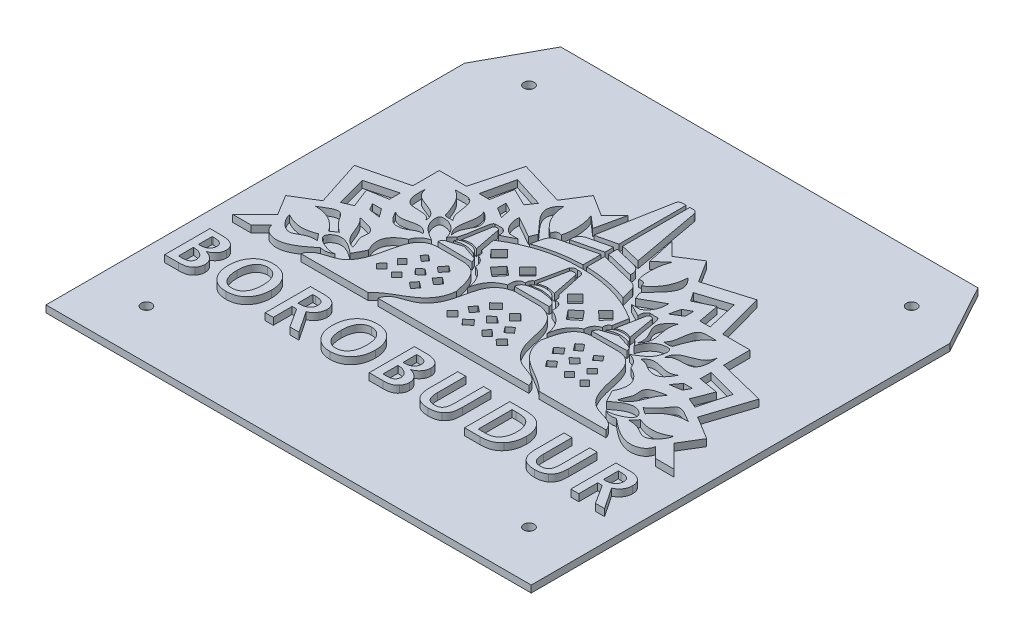
SolidWorks part; units mm, degrees
ref_plane "Front Plane" through (0, 0, 0) normal (0, 0, 1) x (1, 0, 0)
ref_plane "Top Plane" through (0, 0, 0) normal (0, 1, 0) x (1, 0, 0)
ref_plane "Right Plane" through (0, 0, 0) normal (1, 0, 0) x (0, 0, -1)
sketch "Sketch2" plane through (0, 0, 0) normal (0, 1, 0) x (1, 0, 0)
  line L0 (-69.75, 120.33) -> (-69.75, 0)
  line L1 (-69.75, 0) -> (69.75, 0)
  line L2 (69.75, 0) -> (69.75, 120.33)
  line L3 (69.75, 120.33) -> (59.98, 138.2123)
  line L4 (59.98, 138.2123) -> (-59.98, 138.2123)
  line L5 (-59.98, 138.2123) -> (-69.75, 120.33)
  line L6 (-55, 124.11) -> (-55, 14.11) construction
  line L7 (-55, 14.11) -> (55, 14.11) construction
  line L8 (55, 14.11) -> (55, 124.11) construction
  line L9 (55, 124.11) -> (-55, 124.11) construction
  line L10 (0, 14.11) -> (0, 0) construction
  circle A0 centre (-55, 124.11) radius 1.5
  circle A1 centre (55, 124.11) radius 1.5
  circle A2 centre (55, 14.11) radius 1.5
  circle A3 centre (-55, 14.11) radius 1.5
  point P6 (0, 0)
  dimension "D6" = 3
  dimension "D1" = 139.5
  dimension "D2" = 120.33
  dimension "D3" = 118.65
  dimension "D4" = 118.65
  dimension "D5" = 119.96
  dimension "D7" = 110
  dimension "D8" = 110
  dimension "D9" = 14.11
extrude "Boss-Extrude1" add sketch "Sketch2" along normal blind 2
sketch "Sketch5" plane through (0, 2, 0) normal (0, 1, 0) x (1, 0, 0)
  line L0 (-492.273, -111.0065) -> (-56.9397, -111.0065) construction
  line L3 (0, 0) -> (0, 138.2123) construction
  line L4 (59.98, 138.2123) -> (-59.98, 138.2123) construction
  line L5 (-499.4365, -25.4656) -> (-64.1032, -25.4656) construction
  line L6 (0, 47.3754) -> (-21.6859, 47.3754)
  line L7 (-24.6018, 47.3754) -> (-43.8626, 47.3754)
  line L8 (-25.7541, 68.7243) -> (-18.7302, 68.7243)
  line L9 (-22.2422, 68.7243) -> (-22.2422, 47.3754) construction
  line L10 (-3.7057, 68.7243) -> (0, 68.7243)
  line L11 (-19.5144, 78.4449) -> (-18.7302, 74.224)
  line L12 (-1.7255, 82.4366) -> (-3.4837, 74.224)
  line L13 (-1.013, 81.2435) -> (-2.4679, 73.9099)
  line L14 (0, 91.6011) -> (-8.7196, 89.5051)
  line L15 (0, 95.6184) -> (-6.3568, 94.0901)
  line L16 (-6.3568, 94.0901) -> (-2.7736, 113.7579)
  line L17 (-1.4606, 114.8023) -> (0, 114.8023)
  line L18 (0, 90.4895) -> (-10.1933, 87.9731)
  line L19 (-12.4793, 86.3667) -> (-13.4352, 82.7244)
  line L20 (-6.3568, 103.9184) -> (-10.1933, 100.082)
  line L21 (-10.1933, 100.082) -> (-16.2824, 103.9184)
  line L22 (-16.2824, 103.9184) -> (-20.2698, 97.5897)
  line L23 (-20.2698, 97.5897) -> (-33.217, 101.4709)
  line L24 (-33.217, 101.4709) -> (-36.8387, 87.9731)
  line L25 (-36.8387, 87.9731) -> (-44.6751, 87.9731)
  line L26 (-44.6751, 87.9731) -> (-44.6751, 80.3944)
  line L27 (-44.6751, 80.3944) -> (-58.1708, 77.0507)
  line L28 (-58.1708, 77.0507) -> (-53.8631, 63.7358)
  line L29 (-53.8631, 63.7358) -> (-60.5227, 59.6742)
  line L30 (-60.5227, 59.6742) -> (-56.9815, 53.8678)
  line L31 (-56.9815, 53.8678) -> (-63.4739, 47.3754)
  line L32 (-63.4739, 47.3754) -> (-58.1708, 47.3754)
  line L33 (-58.1708, 47.3754) -> (-55.1522, 50.3941)
  line L34 (-46.3062, 54.8983) -> (-44.6751, 52.9547)
  line L35 (-6.3568, 103.9184) -> (-8.1937, 95.6184)
  line L36 (-8.1937, 95.6184) -> (-11.6081, 98.5775)
  line L37 (-30.2456, 87.9731) -> (-29.1015, 94.0901)
  line L38 (-29.1015, 94.0901) -> (-23.9639, 91.6011)
  line L39 (-23.9639, 91.6011) -> (-22.2422, 94.0901)
  line L40 (-22.2422, 94.0901) -> (-31.1681, 96.9522)
  line L41 (-31.1681, 96.9522) -> (-33.217, 87.9731)
  line L42 (-33.217, 87.9731) -> (-30.2456, 87.9731)
  line L43 (-46.0099, 70.1281) -> (-44.9506, 68.2469)
  line L44 (-44.9506, 68.2469) -> (-41.688, 67.7366)
  line L45 (-41.688, 67.7366) -> (-43.4326, 70.1281)
  line L46 (-43.4326, 70.1281) -> (-46.0099, 70.1281)
  line L47 (-50.9674, 65.8317) -> (-48.0862, 67.0605)
  line L48 (-48.0862, 67.0605) -> (-50.2895, 72.681)
  line L49 (-50.2895, 72.681) -> (-44.6751, 73.6456)
  line L50 (-44.6751, 73.6456) -> (-44.6751, 76.7636)
  line L51 (-44.6751, 76.7636) -> (-53.3034, 74.4572)
  line L52 (-53.3034, 74.4572) -> (-50.9674, 65.8317)
  line L53 (-36.8387, 54.5399) -> (-35.0144, 58.0517)
  line L54 (-45.4914, 56.9812) -> (-43.6659, 58.2376)
  line L55 (-22.2422, 72.681) -> (-26.2797, 71.3942)
  line L56 (-27.1911, 70.1281) -> (-17.17, 69.9143)
  line L57 (-22.2422, 72.681) -> (-17.8234, 71.2032)
  line L58 (-26.9657, 89.4844) -> (-26.9657, 87.0105)
  line L59 (-26.9657, 87.0105) -> (-23.9639, 85.1856)
  line L60 (-23.9639, 85.1856) -> (-24.7105, 88.2474)
  line L61 (-24.7105, 88.2474) -> (-26.9657, 89.4844)
  line L62 (0, 56.8345) -> (-1.7255, 58.5599)
  line L63 (-1.7255, 58.5599) -> (0, 59.9061)
  line L64 (-4.57, 62.2541) -> (-2.898, 60.5821)
  line L65 (-2.898, 60.5821) -> (-1.013, 62.4672)
  line L66 (-1.013, 62.4672) -> (-2.6352, 64.0895)
  line L67 (-2.6352, 64.0895) -> (-4.57, 62.2541)
  line L68 (-6.6579, 58.2482) -> (-4.9516, 56.908)
  line L69 (-6.6579, 58.2482) -> (-5.3758, 59.8806)
  line L70 (-4.9516, 56.908) -> (-3.6695, 58.5404)
  line L71 (-5.3758, 59.8806) -> (-3.6695, 58.5404)
  line L72 (-4.3197, 54.3049) -> (-2.898, 52.7842)
  line L73 (-4.3197, 54.3049) -> (-2.5487, 55.9606)
  line L74 (-2.898, 52.7842) -> (-1.127, 54.4399)
  line L75 (-2.5487, 55.9606) -> (-1.127, 54.4399)
  line L76 (-8.7196, 54.3049) -> (-7.1489, 52.6248)
  line L77 (-8.7196, 54.3049) -> (-7.0939, 55.8247)
  line L78 (-7.1489, 52.6248) -> (-5.5232, 54.1446)
  line L79 (-7.0939, 55.8247) -> (-5.5232, 54.1446)
  line L80 (-21.1518, 55.8377) -> (-19.4037, 54.4647)
  line L81 (-21.1518, 55.8377) -> (-19.8599, 57.4825)
  line L82 (-19.4037, 54.4647) -> (-18.1117, 56.1095)
  line L83 (-19.8599, 57.4825) -> (-18.1117, 56.1095)
  line L84 (-18.9101, 60.1733) -> (-17.0591, 58.7194)
  line L85 (-18.9101, 60.1733) -> (-17.6103, 61.8282)
  line L86 (-17.0591, 58.7194) -> (-15.7593, 60.3743)
  line L87 (-17.6103, 61.8282) -> (-15.7593, 60.3743)
  line L88 (-20.9944, 63.7167) -> (-19.4037, 62.4672)
  line L89 (-20.9944, 63.7167) -> (-19.5144, 65.6009)
  line L90 (-19.4037, 62.4672) -> (-17.9236, 64.3515)
  line L91 (-19.5144, 65.6009) -> (-17.9236, 64.3515)
  line L92 (-26.2797, 64.0895) -> (-24.6018, 62.7715)
  line L93 (-26.2797, 64.0895) -> (-25.2216, 65.4366)
  line L94 (-24.6018, 62.7715) -> (-23.5437, 64.1187)
  line L95 (-25.2216, 65.4366) -> (-23.5437, 64.1187)
  line L96 (-22.2422, 61.464) -> (-23.7093, 60.1733)
  line L97 (-23.7093, 60.1733) -> (-22.2422, 58.5404)
  line L98 (-22.2422, 58.5404) -> (-20.5282, 60.0802)
  line L99 (-20.5282, 60.0802) -> (-22.2422, 61.464)
  line L100 (-28.7512, 60.0802) -> (-27.1911, 58.5404)
  line L101 (-28.7512, 60.0802) -> (-27.4069, 61.4423)
  line L102 (-27.1911, 58.5404) -> (-25.8467, 59.9024)
  line L103 (-27.4069, 61.4423) -> (-25.8467, 59.9024)
  line L104 (-26.2797, 55.8377) -> (-24.8885, 54.4647)
  line L105 (-26.2797, 55.8377) -> (-24.7708, 57.3665)
  line L106 (-24.8885, 54.4647) -> (-23.3797, 55.9934)
  line L107 (-24.7708, 57.3665) -> (-23.3797, 55.9934)
  line L108 (-30.6365, 55.8377) -> (-29.2453, 54.4647)
  line L109 (-30.6365, 55.8377) -> (-29.0938, 57.4008)
  line L110 (-29.2453, 54.4647) -> (-27.7026, 56.0277)
  line L111 (-29.0938, 57.4008) -> (-27.7026, 56.0277)
  line L112 (-17.5779, 75.7199) -> (-15.5694, 73.6456)
  line L113 (-17.5779, 75.7199) -> (-15.1083, 78.1111)
  line L114 (-15.5694, 73.6456) -> (-13.0998, 76.0368)
  line L115 (-15.1083, 78.1111) -> (-13.0998, 76.0368)
  line L116 (-13.2677, 71.2568) -> (-10.6976, 69.1502)
  line L117 (-13.2677, 71.2568) -> (-11.093, 73.9099)
  line L118 (-10.6976, 69.1502) -> (-8.5229, 71.8032)
  line L119 (-11.093, 73.9099) -> (-8.5229, 71.8032)
  line L120 (-9.1064, 75.5043) -> (-6.9213, 73.2802)
  line L121 (-9.1064, 75.5043) -> (-6.6904, 77.8778)
  line L122 (-6.9213, 73.2802) -> (-4.5053, 75.6536)
  line L123 (-6.6904, 77.8778) -> (-4.5053, 75.6536)
  line L124 (-23.3797, 82.7244) -> (-21.1518, 82.7244)
  line L125 (-16.2824, 82.29) -> (-20.0337, 80.3944)
  line L126 (-21.4739, 87.796) -> (-15.3829, 84.3725)
  line L127 (-15.3829, 84.3725) -> (-14.6072, 86.3667)
  line L128 (-18.7302, 82.29) -> (-16.2824, 82.29)
  line L129 (0, 114.8023) -> (0, 95.6184)
  line L130 (0, 91.6011) -> (0, 94.0901)
  line L131 (0, 94.0901) -> (-6.9213, 92.4263)
  line L132 (0, 90.4895) -> (0, 85.1856)
  line L133 (0, 84.0727) -> (0, 83.0699)
  line L134 (0, 82.0012) -> (0, 74.4572)
  line L135 (0, 73.9099) -> (0, 72.8637)
  line L136 (0, 72.5184) -> (0, 69.9143)
  line L137 (0, 68.7243) -> (0, 47.3754)
  line L138 (-24.2404, 73.9099) -> (-22.9425, 81.459)
  line L139 (-19.8599, 73.8153) -> (-21.3384, 81.459)
  spline S0 degree 3 poles (-43.8626, 47.3754) (-42.9521, 50.5844) (-36.4958, 50.0974) (-31.3645, 59.4416) (-31.9209, 68.6588) (-25.7541, 68.7243) knots 0 0 0 0 0.285538 0.498981 1 1 1 1
  spline S1 degree 3 poles (-12.1467, 60.4138) (-13.0855, 64.6613) (-13.8787, 68.6728) (-18.7302, 68.7243) knots 0.60584 0.60584 0.60584 0.60584 1 1 1 1
  spline S2 degree 3 poles (-24.6018, 47.3754) (-20.4059, 51.9406) (-12.8785, 52.3753) (-12.1467, 60.4138) knots 0 0 0 0 1 1 1 1
  spline S3 degree 3 poles (-21.6859, 47.3754) (-21.0603, 50.4734) (-15.3356, 50.4348) (-8.8142, 58.6677) (-10.5494, 67.4068) (-3.7057, 68.7243) knots 0 0 0 0 0.270547 0.473964 1 1 1 1
  spline S4 degree 2 poles (0, 84.0727) (-10.6051, 84.197) (-19.5144, 78.4449) knots 0 0 0 1 1 1
  spline S5 degree 2 poles (-18.7302, 74.224) (-17.5047, 73.6029) (-17.8234, 72.3602) knots 0 0 0 1 1 1
  spline S6 degree 2 poles (-17.8234, 72.3602) (-15.651, 71.6726) (-15.5694, 69.3242) knots 0 0 0 1 1 1
  spline S7 degree 2 poles (-15.5694, 69.3242) (-11.7671, 67.3735) (-11.4229, 62.8919) knots 0 0 0 1 1 1
  spline S8 degree 2 poles (-11.4229, 62.8919) (-10.8067, 67.7648) (-6.3568, 69.3242) knots 0 0 0 1 1 1
  spline S9 degree 2 poles (-4.3084, 72.3602) (-6.6845, 72.4435) (-6.3568, 69.3242) knots 0 0 0 1 1 1
  spline S10 degree 2 poles (-4.3084, 72.3602) (-4.4719, 73.5979) (-3.4837, 74.224) knots 0 0 0 1 1 1
  spline S11 degree 2 poles (0, 83.0699) (-1.1111, 83.4064) (-1.7255, 82.4366) knots 0 0 0 1 1 1
  spline S12 degree 3 poles (0, 82.0012) (-0.5463, 82.1465) (-0.8839, 81.8939) (-1.013, 81.2435) knots 0 0 0 0 1 1 1 1
  spline S13 degree 2 poles (0, 74.4572) (-1.2543, 74.2752) (-2.4679, 73.9099) knots 0 0 0 1 1 1
  spline S14 degree 2 poles (0, 73.9099) (-2.061, 73.9775) (-3.2599, 72.3602) knots 0 0 0 1 1 1
  spline S15 degree 2 poles (-3.2599, 72.3602) (-1.6557, 72.7761) (0, 72.8637) knots 0 0 0 1 1 1
  spline S16 degree 3 poles (0, 72.5184) (-1.8552, 72.1989) (-4.9711, 72.3963) (-4.9908, 69.9143) knots 0 0 0 0 1 1 1 1
  spline S17 degree 1 poles (0, 69.9143) (-4.9908, 69.9143) knots 0 0 1 1
  spline S18 degree 2 poles (-2.7736, 113.7579) (-2.545, 114.8416) (-1.4606, 114.8023) knots 0 0 0 1 1 1
  spline S19 degree 2 poles (-10.1933, 87.9731) (-11.7123, 87.6861) (-12.4793, 86.3667) knots 0 0 0 1 1 1
  spline S20 degree 2 poles (-13.4352, 82.7244) (-6.9507, 85.146) (0, 85.1856) knots 0 0 0 1 1 1
  spline S21 degree 3 poles (-55.1522, 50.3941) (-54.8966, 48.4539) (-49.6723, 45.6985) (-44.8611, 49.7991) (-42.5456, 51.7133) knots 0 0 0 0 0.336939 1 1 1 1
  spline S22 degree 2 poles (-55.1522, 55.4537) (-50.8462, 52.8644) (-46.3062, 54.8983) knots 0 0 0 1 1 1
  spline S23 degree 3 poles (-55.1522, 55.4537) (-55.0749, 53.8847) (-52.1611, 50.1271) (-48.2771, 52.3365) (-46.3808, 53.264) (-44.6751, 52.9547) knots 0 0 0 0 0.513802 0.617376 1 1 1 1
  spline S24 degree 2 poles (-11.6081, 98.5775) (-9.9467, 94.1512) (-11.093, 89.5051) knots 0 0 0 1 1 1
  spline S25 degree 2 poles (-17.8234, 96.9522) (-17.5779, 91.4078) (-13.1084, 88.2984) knots 0 0 0 1 1 1
  spline S26 degree 2 poles (-11.093, 89.5051) (-12.8256, 90.0868) (-13.1084, 88.2984) knots 0 0 0 1 1 1
  spline S27 degree 3 poles (-17.8234, 96.9522) (-22.4568, 92.8593) (-16.859, 89.4672) (-14.6072, 86.3667) knots 0 0 0 0 1 1 1 1
  spline S28 degree 3 poles (-38.9362, 52.2621) (-40.0045, 51.7087) (-47.0477, 54.0125) (-41.8461, 58.7473) (-38.3314, 55.7308) (-36.8387, 54.5399) knots 0 0 0 0 0.430134 0.559823 1 1 1 1
  spline S29 degree 2 poles (-42.5456, 51.7133) (-40.661, 51.1729) (-38.9362, 52.2621) knots 0 0 0 1 1 1
  spline S30 degree 2 poles (-35.0144, 58.0517) (-38.0223, 63.5186) (-31.9435, 66.4334) knots 0 0 0 1 1 1
  spline S31 degree 2 poles (-31.9435, 66.4334) (-31.0893, 68.9745) (-28.4778, 69.5574) knots 0 0 0 1 1 1
  spline S32 degree 3 poles (-53.6634, 61.3327) (-52.0615, 61.3174) (-48.9555, 60.6674) (-46.5857, 58.5712) (-45.4914, 56.9812) knots 0.005198 0.005198 0.005198 0.005198 0.462661 1 1 1 1
  spline S33 degree 3 poles (-53.6634, 61.3327) (-53.1598, 61.3764) (-51.0222, 63.1399) (-48.1912, 63.6957) (-46.5269, 60.5729) (-45.0294, 59.3254) (-43.6659, 58.2376) knots 0.01154 0.01154 0.01154 0.01154 0.305761 0.43615 0.629288 0.980308 0.980308 0.980308 0.980308
  spline S34 degree 3 poles (-44.3415, 64.8566) (-41.415, 62.5208) (-42.1713, 57.6443) (-38.0292, 56.4621) knots 0 0 0 0 1 1 1 1
  spline S35 degree 3 poles (-44.3415, 64.8566) (-43.3621, 64.5853) (-38.4355, 64.1691) (-39.7393, 59.4545) (-38.5212, 58.5122) (-38.0292, 56.4621) knots 0 0 0 0 0.474827 0.654779 1 1 1 1
  spline S36 degree 2 poles (-26.2797, 71.3942) (-27.1006, 71.0073) (-27.1911, 70.1281) knots 0 0 0 1 1 1
  spline S37 degree 2 poles (-17.17, 69.9143) (-17.41, 70.6055) (-17.8234, 71.2032) knots 0 0 0 1 1 1
  spline S38 degree 3 poles (-28.4778, 69.5574) (-30.532, 70.8025) (-33.2273, 72.1143) (-33.496, 76.7183) (-29.6669, 76.9172) (-27.6003, 74.7511) (-26.9657, 72.3602) knots 0 0 0 0 0.406747 0.533053 0.591311 1 1 1 1
  spline S39 degree 3 poles (-40.6457, 71.3942) (-40.149, 70.4981) (-38.7583, 67.6743) (-34.408, 68.2779) (-32.8852, 70.1036) (-31.2827, 69.9143) knots 0 0 0 0 0.360983 0.637936 1 1 1 1
  spline S40 degree 3 poles (-40.6457, 71.3942) (-37.5907, 68.9893) (-33.7089, 73.6061) (-31.2827, 69.9143) knots 0 0 0 0 1 1 1 1
  spline S41 degree 3 poles (-41.9555, 81.2435) (-42.2243, 79.8321) (-42.3033, 73.0878) (-35.3191, 76.123) (-34.2379, 73.6456) knots 0 0 0 0 0.454885 1 1 1 1
  spline S42 degree 3 poles (-41.9555, 81.2435) (-41.3021, 76.4362) (-34.3542, 78.6828) (-34.2379, 73.6456) knots 0 0 0 0 1 1 1 1
  spline S43 degree 3 poles (-37.6021, 85.5111) (-36.2893, 85.3647) (-32.5423, 86.252) (-31.55, 81.2084) (-31.5002, 78.8462) (-30.2456, 77.5331) knots 0 0 0 0 0.366527 0.616998 1 1 1 1
  spline S44 degree 3 poles (-37.6021, 85.5111) (-35.3214, 84.0723) (-34.43, 82.5142) (-32.8279, 78.4091) (-32.8292, 77.5539) (-31.8585, 77.4446) (-30.2456, 77.5331) knots 0 0 0 0 0.537998 0.5989 0.784193 1 1 1 1
  spline S45 degree 3 poles (-26.7833, 73.6456) (-29.9664, 76.7264) (-26.2408, 80.5894) (-27.9589, 84.0727) knots 0 0 0 0 1 1 1 1
  spline S46 degree 3 poles (-27.9589, 84.0727) (-26.7849, 83.491) (-24.1776, 81.0218) (-26.3254, 77.2487) (-27.2945, 75.2172) (-26.7833, 73.6456) knots 0 0 0 0 0.40452 0.640919 1 1 1 1
  spline S47 degree 2 poles (-26.9657, 72.3602) (-26.4261, 73.2935) (-25.5469, 73.9099) knots 0 0 0 1 1 1
  spline S48 degree 3 poles (-25.5469, 73.9099) (-24.5336, 77.1889) (-24.6874, 79.2624) (-23.839, 82.4674) (-23.3797, 82.7244) knots 0 0 0 0 0.838059 1 1 1 1
  spline S49 degree 2 poles (-21.1518, 82.7244) (-19.8203, 82.0978) (-20.0337, 80.3944) knots 0 0 0 1 1 1
  spline S50 degree 3 poles (-21.4739, 87.796) (-21.6513, 85.7069) (-20.7412, 83.2153) (-18.7302, 82.29) knots 0 0 0 0 1 1 1 1
  spline S51 degree 2 poles (-6.9213, 92.4263) (-8.9157, 91.7486) (-8.7196, 89.5051) knots 0 0 0 1 1 1
  spline S52 degree 2 poles (-25.0807, 72.5184) (-22.0209, 73.768) (-19.0758, 72.1843) knots 0 0 0 1 1 1
  spline S53 degree 2 poles (-24.2404, 73.9099) (-22.0526, 75.0527) (-19.8599, 73.8153) knots 0 0 0 1 1 1
  spline S54 degree 3 poles (-25.0807, 72.5184) (-24.9657, 73.5121) (-22.2153, 74.2838) (-19.7538, 73.7674) (-19.0758, 72.1843) knots 0 0 0 0 0.375201 1 1 1 1
  spline S55 degree 3 poles (-22.9425, 81.459) (-22.8734, 82.2381) (-21.4069, 82.247) (-21.3384, 81.459) knots 0 0 0 0 1 1 1 1
extrude "Boss-Extrude6" add sketch "Sketch5" along normal blind 2 contours L7 S2 S1 L8 S0 L109 L111 L110 L108 L105 L107 L106 L104 L101 L103 L102 L100 L93 L95 L94 L92 L89 L91 L90 L88 L85 L87 L86 L84 L81 L83 L82 L80 L99 L98 L97 L96 | S3 L6 L137 L62 L63 L10 L67 L66 L65 L64 L69 L71 L70 L68 L73 L75 L74 L72 L77 L79 L78 L76 | S11 L133 S4 L11 S5 S6 S7 S8 S9 S10 L12 L121 L123 L122 L120 L117 L119 L118 L116 L113 L115 L114 L112 | S13 L134 S12 L13 | S14 S15 L135 | S17 L136 S16 | L19 S20 L132 L18 S19 | S18 L16 L15 L129 L17 | L131 S51 L14 L130 | S55 L138 S53 L139 | S54 S52 | L56 S37 L57 L55 S36 | S50 L126 L127 S27 S25 S26 S24 L36 L35 L20 L21 L22 L23 L24 L25 L26 L27 L28 L29 L30 L31 L32 L33 S21 S29 S28 L53 S30 S31 S38 S47 S48 L124 S49 L125 L128 S44 S43 S23 S22 L34 L61 L60 L59 L58 L52 L51 region at (-7.1497, 2, -55.8216) region at (-25.1873, 2, -57.442) region at (-10.1075, 2, -76.1716) region at (-0.8987, 2, -77.4798) region at (-4.2282, 2, -91.8003) region at (-2.3815, 2, -103.4294) region at (-6.1376, 2, -86.6784) region at (-8.0602, 2, -99.9421) region at (-22.1691, 2, -71.0071) region at (-1.3183, 2, -73.1828) region at (-2.2004, 2, -71.0201) region at (-22.0913, 2, -77.4687) region at (-22.1381, 2, -73.2833)
sketch "Sketch4" plane through (0, 2, 0) normal (0, 1, 0) x (1, 0, 0)
  text T0 "BOROBUDUR" font "Lucida Sans Unicode" height 13
extrude "Boss-Extrude3" add sketch "Sketch4" along normal blind 2
mirror "Mirror1" about plane through (0, 4, 0) normal (1, 0, 0) of "Boss-Extrude6"
sketch "Sketch6" plane through (0, 4, 0) normal (0, 1, 0) x (1, 0, 0)
  line L0 (-0.5281, 116.4003) -> (0.5281, 116.4003)
  line L1 (-1.4606, 114.8023) -> (1.4606, 114.8023) construction
  line L2 (0, 114.8023) -> (0, 116.4003) construction
  line L3 (-0.5281, 116.4003) -> (-0.5281, 84.6919)
  line L4 (-0.5281, 84.6919) -> (0.5281, 84.6919)
  line L5 (0.5281, 84.6919) -> (0.5281, 116.4003)
extrude "Cut-Extrude1" cut sketch "Sketch6" against normal up to surface (2 mm away) up to face at (25.0807, 2, -72.5184)
